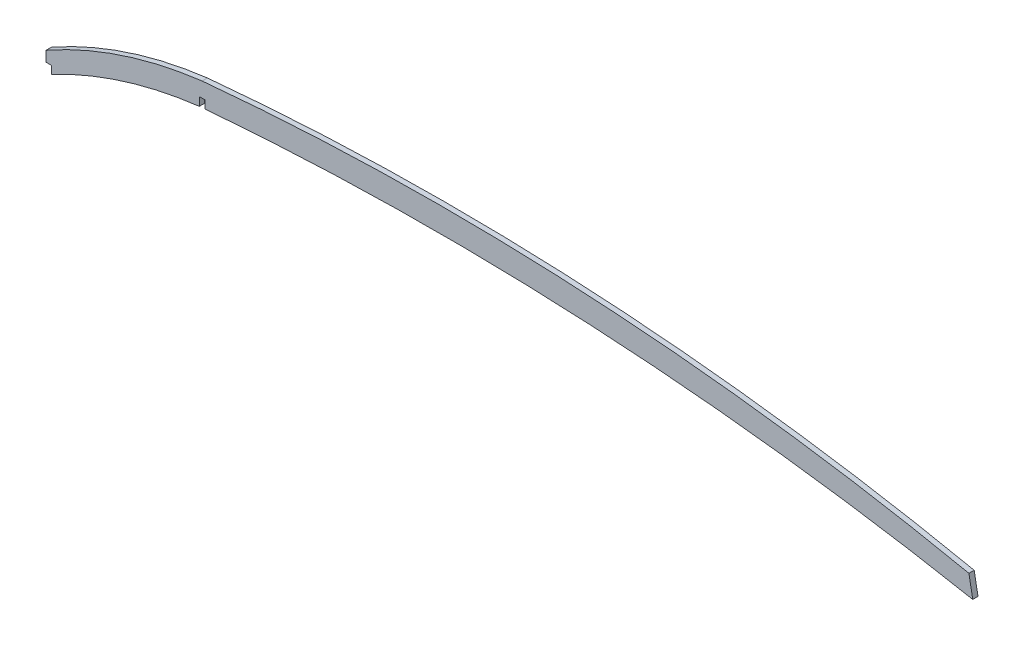
SolidWorks part; units mm, degrees
material "Balsa"
ref_plane "Front Plane" through (0, 0, 0) normal (0, 0, 1) x (1, 0, 0)
ref_plane "Top Plane" through (0, 0, 0) normal (0, 1, 0) x (1, 0, 0)
ref_plane "Right Plane" through (0, 0, 0) normal (1, 0, 0) x (0, 0, -1)
sketch "Sketch1" plane through (0, 0, 0) normal (0, 0, 1) x (1, 0, 0)
  line L2 (0, 0) -> (0, 169.3685) construction
  line L4 (93.98, 106.68) -> (556.5761, 106.68) construction
  line L9 (0, 106.68) -> (93.98, 106.68) construction
  line L14 (555.6382, 111.8229) -> (555.6382, 106.68) construction
  line L17 (555.6382, 111.8229) -> (557.917, 99.3265)
  line L19 (0, 106.68) -> (0, 93.98)
  line L20 (93.98, 137.668) -> (93.98, 123.7947) construction
  arc A6 (0, 106.68) -> (93.98, 137.668) centre (125.0054, -114.43) cw
  arc A8 (93.98, 137.668) -> (555.6382, 111.8229) centre (239.5165, -1398.7972) cw
  arc A9 (0, 93.98) -> (93.98, 123.7947) centre (122.3372, -128.6174) cw
  arc A25 (93.98, 123.7947) -> (557.917, 99.3265) centre (236.8486, -1577.8511) cw
  dimension "D4" = 254
  dimension "D2" = 93.98
  dimension "D8" = 1543.3426
  dimension "D9" = 100.334
  dimension "D3" = 30.988
  dimension "D12" = 254
  dimension "D14" = 1707.6328
  dimension "D1" = 106.68
  dimension "D5" = 462.5961
  dimension "D6" = 0.9378
  dimension "D7" = 5.1429
  dimension "D10" = 12.7025
  dimension "D11" = 12.7
  dimension "D13" = 13.8733
extrude "Boss-Extrude1" add sketch "Sketch1" against normal blind 3.175 contours A9 A25 L17 A8 A6 L19 region at (551.2665, 104.5698, 0)
sketch "Sketch2" plane through (0, 0, -3.175) normal (0, 0, -1) x (-1, 0, 0)
  line L0 (0, 0) -> (0, 93.98) construction
  line L1 (0, 0) -> (-93.98, 0) construction
  line L2 (-93.98, 0) -> (-93.98, 122.4225) construction
  line L4 (0, 93.98) -> (-3.3528, 93.98)
  line L5 (0, 93.98) -> (0, 100.457)
  line L6 (0, 100.457) -> (-3.3528, 100.457)
  line L7 (-3.3528, 93.98) -> (-3.3528, 100.457)
  line L9 (-95.6691, 122.4225) -> (-92.2909, 122.4225)
  line L10 (-95.6691, 122.4225) -> (-95.6691, 128.6963)
  line L11 (-95.6691, 128.6963) -> (-92.2909, 128.6963)
  line L12 (-92.2909, 122.4225) -> (-92.2909, 128.6963)
  point P5 (0, 0)
  dimension "D1" = 93.98
  dimension "D2" = 6.477
  dimension "D3" = 3.3528
  dimension "D4" = 93.98
  dimension "D5" = 122.4225
  dimension "D6" = 3.3782
  dimension "D7" = 6.2738
extrude "Cut-Extrude1" cut sketch "Sketch2" against normal through all
equation "\"slotwidth\"=0.167708"
